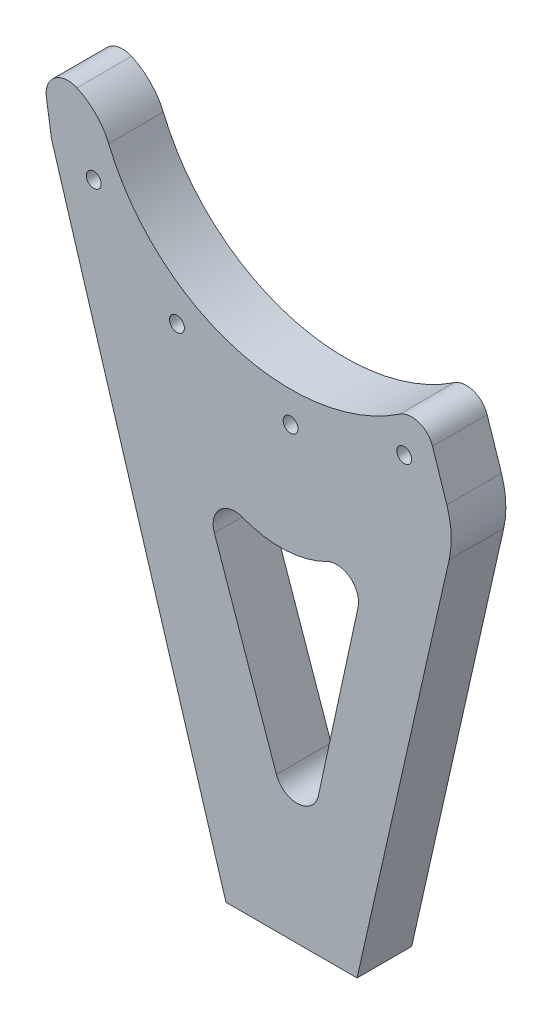
SolidWorks part; units mm, degrees
ref_plane "Front Plane" through (0, 0, 0) normal (0, 0, 1) x (1, 0, 0)
ref_plane "Top Plane" through (0, 0, 0) normal (0, 1, 0) x (1, 0, 0)
ref_plane "Right Plane" through (0, 0, 0) normal (1, 0, 0) x (0, 0, -1)
sketch "Sketch1" plane through (0, 0, 0) normal (0, 0, 1) x (1, 0, 0)
  line L1 (52, 0) -> (57.5, 0)
  line L2 (-56.8494, -8.625) -> (-54.7139, -22.7011)
  line L4 (-14.7864, -154.0477) -> (15.2136, -154.0477)
  line L5 (30.2586, -33.3079) -> (37.4888, -55.2692)
  line L7 (-14.7864, -154.0477) -> (15.2136, -154.0477)
  line L9 (-54.7139, -22.7011) -> (-14.7864, -154.0477)
  line L10 (37.4888, -55.2692) -> (15.2136, -154.0477)
  arc A1 (-41.6158, -17.1208) -> (30.2586, -33.3079) centre (0, 0) ccw
  arc A3 (-51.2334, -8.8959) -> (32.6241, -40.4928) centre (0, 0) ccw construction
  arc A6 (-51.2334, -8.8959) -> (32.6241, -40.4928) centre (0, 0) ccw construction
  arc A8 (-51.2334, -8.8959) -> (0, -52) centre (0, 0) ccw construction
  arc A11 (-56.8494, -8.625) -> (-41.6158, -17.1208) centre (-54.7139, -22.7011) cw
  circle A13 centre (0, -52) radius 1.7
  circle A14 centre (-26, -45.0333) radius 1.7
  circle A15 centre (-45.0333, -26) radius 1.7
  circle A24 centre (26, -45.0333) radius 1.7
  circle A25 centre (-45.0333, 26) radius 1.7 [skipped]
  circle A26 centre (-26, 45.0333) radius 1.7 [skipped]
  circle A27 centre (0, 52) radius 1.7 [skipped]
  circle A28 centre (45.0333, 26) radius 1.7 [skipped]
  circle A29 centre (26, 45.0333) radius 1.7 [skipped]
  arc A30 (-51.9722, -1.6998) -> (-50.3, 0) centre (-52, 0) ccw [skipped]
  arc A31 (50.3, 0) -> (51.9722, -1.6998) centre (52, 0) ccw [skipped]
  arc A32 (56.874, -8.4618) -> (57.5, 0) centre (0, 0) ccw
  circle A33 centre (45.0333, -26) radius 1.7 [skipped]
  point P26 (0, 0)
  point P32 (0, 0)
  point P50 (0, 0)
  dimension "D1" = 90
  dimension "D5" = 104
  dimension "D6" = 3.4
  dimension "D4" = 30
  dimension "D7" = 3
  dimension "D8" = 12
extrude "Boss-Extrude1" add sketch "Sketch1" along normal blind 12.5 contours A32 L1 A1 L2 A13 A14 A15 A24 region at (-5.673, -84.2355, 0)
fillet "Fillet4" radius 5 1 edges at (-56.8494, -8.625, 6.25)
fillet "Fillet5" radius 5 1 edges at (-54.7139, -22.7011, 6.25)
fillet "Fillet6" radius 5 1 edges at (30.2586, -33.3079, 6.25)
fillet "Fillet7" radius 20 1 edges at (37.4888, -55.2692, 6.25)
sketch "Sketch2" plane through (0, -154.0477, 0) normal (0, -1, 0) x (-1, 0, 0)
  line L0 (-15.2136, 0) -> (14.7864, -12.5) construction
  circle A0 centre (-0.2136, -6.25) radius 1.745
  point P6 (-0.2136, -6.25)
  dimension "D1" = 3.49
extrude "Cut-Extrude1" cut sketch "Sketch2" against normal blind 10
sketch "Sketch3" plane through (0, 0, 0) normal (0, 0, -1) x (-1, 0, 0)
  line L0 (-19.0101, -64.0145) -> (-2.6019, -139.7266)
  line L1 (-2.6019, -139.7266) -> (24.5888, -61.6705)
  arc A0 (24.5888, -61.6705) -> (-19.0101, -64.0145) centre (2.3091, -53.9093) cw
extrude "Cut-Extrude2" cut sketch "Sketch3" against normal blind 35
fillet "Fillet8" radius 5 1 edges at (2.6019, -139.7266, 6.25)
fillet "Fillet9" radius 5 2 edges at (-24.5888, -61.6705, 6.25) (19.0101, -64.0145, 6.25)
